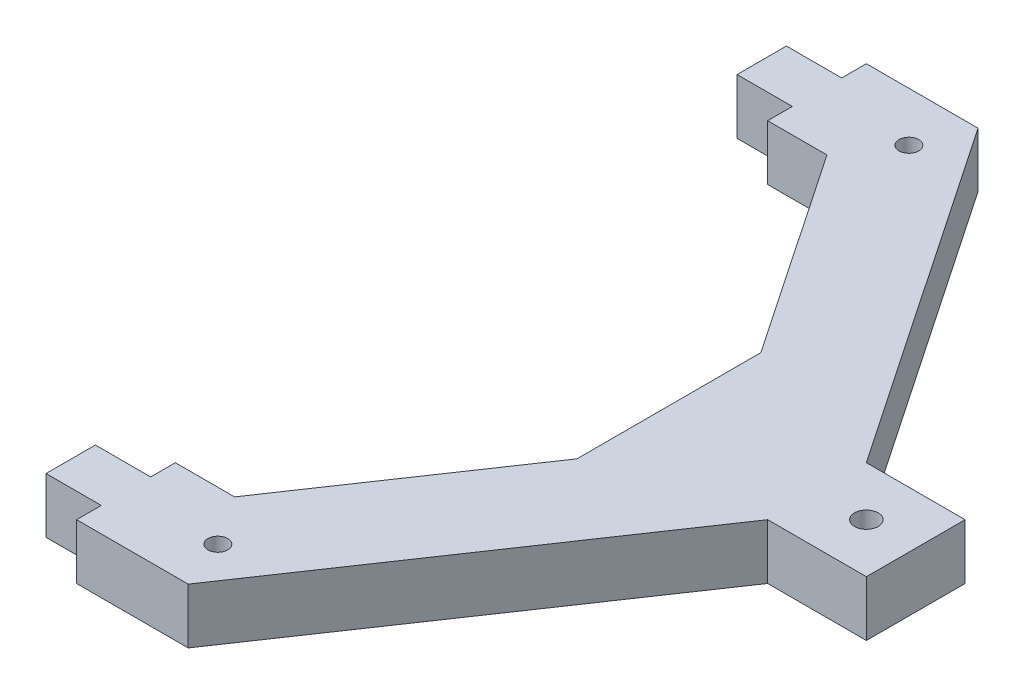
SolidWorks part; units mm, degrees
ref_plane "Front Plane" through (0, 0, 0) normal (0, 0, 1) x (1, 0, 0)
ref_plane "Top Plane" through (0, 0, 0) normal (0, 1, 0) x (1, 0, 0)
ref_plane "Right Plane" through (0, 0, 0) normal (1, 0, 0) x (0, 0, -1)
sketch "Sketch1" plane through (0, 0, 0) normal (0, 1, 0) x (1, 0, 0)
  line L0 (12.5, 25) -> (12.5, 0) construction
  line L1 (12.5, 0) -> (25, 0) construction
  line L2 (0, 12.5) -> (0, 25)
  line L3 (0, 25) -> (25, 25)
  line L4 (25, 12.5) -> (25, 25)
  line L5 (12.5, 0) -> (12.5, 12.5) construction
  line L6 (12.5, 12.5) -> (0, 12.5) construction
  line L7 (12.5, 12.5) -> (-87.5, 12.5) construction
  line L8 (0, 25) -> (-59.2343, 112.5)
  line L9 (-59.2343, 112.5) -> (-87.5, 112.5)
  line L10 (-87.5, 112.5) -> (-87.5, 87.5)
  line L11 (-87.5, 87.5) -> (-72.5, 87.5)
  line L12 (-72.5, 87.5) -> (-37.5, 35.7985)
  line L13 (-37.5, 35.7985) -> (-37.5, 12.5)
  line L14 (-37.5, 12.5) -> (0, 12.5)
  line L15 (0, 12.5) -> (0, 25)
  line L16 (-87.5, 87.5) -> (-87.5, 12.5) construction
  line L17 (0, 0) -> (12.5, 0) construction
  line L18 (0, 25) -> (25, 25)
  line L19 (0, 25) -> (0, 12.5)
  line L20 (0, 12.5) -> (25, 12.5)
  line L21 (25, 25) -> (25, 12.5)
  line L22 (25, 0) -> (25, 12.5) construction
  line L23 (0, 0) -> (0, 12.5) construction
  arc A0 (9.5, 12.5) -> (15.5, 12.5) centre (12.5, 12.5) cw
  dimension "D9" = 3
  dimension "D1" = 25
  dimension "D2" = 25
  dimension "D3" = 100
  dimension "D4" = 50
  dimension "D5" = 25
  dimension "D6" = 75
  dimension "D7" = 25
  dimension "D8" = 15
extrude "Boss-Extrude1" add sketch "Sketch1" along normal blind 14 contours L13 L14 L2 L8 L9 L10 L11 L12 | L2 L20 L4 L3 region at (-42.7836, 0, -62.4735) region at (12.5, 0, -18.9858)
sketch "Sketch2" plane through (0, 14, 0) normal (0, 1, 0) x (1, 0, 0)
  line L0 (-87.5, 100) -> (-87.5, 112.5) construction
  line L1 (-101.5, 106.25) -> (-87.5, 106.25)
  line L2 (-101.5, 106.25) -> (-101.5, 93.75)
  line L3 (-101.5, 93.75) -> (-87.5, 93.75)
  line L4 (-87.5, 106.25) -> (-87.5, 93.75)
  line L5 (-87.5, 112.5) -> (-87.5, 87.5) construction
  point P9 (-87.5, 100)
  dimension "D1" = 12.5
  dimension "D2" = 14
extrude "Boss-Extrude2" add sketch "Sketch2" against normal up to surface (14 mm away) up to face at (-27.8849, 0, -48.9817)
mirror "Mirror1" about plane through (0, 14, -12.5) normal (0, 0, -1) of bodies 102
sketch "Sketch3" plane through (0, 14, 0) normal (0, 1, 0) x (1, 0, 0)
  line L0 (-59.2343, -87.5) -> (-87.5, -87.5) construction
  line L1 (-59.2343, 112.5) -> (-87.5, 112.5) construction
  point P0 (-64.2343, 100)
  point P1 (-64.2343, -75)
  dimension "D1" = 5
  dimension "D2" = 12.5
  dimension "D3" = 12.5
  dimension "D4" = 5
hole_wizard "Hole1" positions "Sketch4" profile "Sketch5" legacy end condition through all
sketch "Sketch4" plane through (0, 14, 0) normal (0, 1, 0) x (1, 0, 0)
  point P0 (-64.2343, 100)
  point P3 (-64.2343, -75)
sketch "Sketch5" plane through (-64.2343, 14, -100) normal (1, 0, 0) x (0, 0, 1)
  line L0 (0, 0) -> (0, 14)
  line L1 (0, 14) -> (2.5, 14)
  line L2 (2.5, 14) -> (2.5, 0)
  line L3 (2.5, 0) -> (0, 0)
  line L4 (0, 110) -> (0, -10) construction
  dimension "Diameter" = 5
  dimension "Depth" = 14
equation "\"ply\"= 14mm"
equation "\"D1@Boss-Extrude1\"=\"ply\""
equation "\"D2@Sketch2\"=\"ply\""
